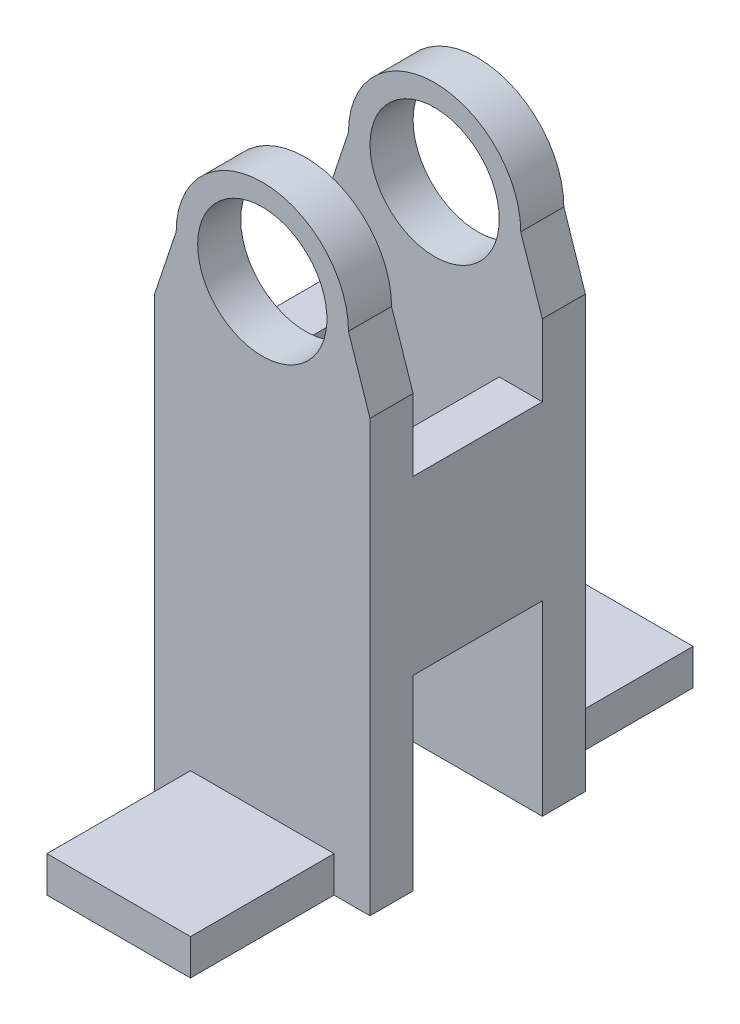
SolidWorks part; units mm, degrees
ref_plane "Front Plane" through (0, 0, 0) normal (0, 0, 1) x (1, 0, 0)
ref_plane "Top Plane" through (0, 0, 0) normal (0, 1, 0) x (1, 0, 0)
ref_plane "Right Plane" through (0, 0, 0) normal (1, 0, 0) x (0, 0, -1)
sketch "Sketch1" plane through (0, 0, 0) normal (0, 1, 0) x (1, 0, 0)
  line L0 (4.5, -4.5) -> (4.5, 4.5)
  line L1 (7.5, -7.5) -> (-7.5, -7.5)
  line L2 (7.5, -7.5) -> (7.5, 7.5)
  line L3 (7.5, 7.5) -> (-7.5, 7.5)
  line L4 (-7.5, -7.5) -> (-7.5, 7.5)
  line L5 (7.5, -7.5) -> (-7.5, 7.5) construction
  line L6 (7.5, 7.5) -> (-7.5, -7.5) construction
  line L7 (4.5, 4.5) -> (-4.5, 4.5)
  line L8 (-4.5, -4.5) -> (-4.5, 4.5)
  line L9 (4.5, -4.5) -> (-4.5, -4.5)
  point P0 (0, 0)
  dimension "D1" = 15
  dimension "D2" = 15
  dimension "D3" = 3
extrude "Boss-Extrude1" add sketch "Sketch1" along normal blind 30
sketch "Sketch3" plane through (0, 0, -7.5) normal (0, 0, -1) x (-1, 0, 0)
  line L0 (-7.5, 30) -> (7.5, 30) construction
  line L1 (-6, 34.5) -> (-7.5, 30)
  line L2 (-7.5, 30) -> (7.5, 30)
  line L3 (7.5, 30) -> (6, 34.5)
  line L4 (7.5, 30) -> (7.5, 0) construction
  line L5 (-7.5, 30) -> (7.5, 30)
  line L6 (-7.5, 30) -> (-7.5, 29)
  line L7 (-7.5, 29) -> (7.5, 29)
  line L8 (7.5, 30) -> (7.5, 29)
  circle A0 centre (0, 34.5) radius 4.5
  arc A1 (-6, 34.5) -> (6, 34.5) centre (0, 34.5) cw
  line M10 (7.5, 0) -> (7.5, 30)
  line M11 (7.5, 30) -> (-7.5, 30)
  line M12 (-7.5, 30) -> (-7.5, 0)
  dimension "D1" = 9
  dimension "D2" = 6
  dimension "D3" = 1
extrude "Boss-Extrude3" add sketch "Sketch3" against normal up to surface (3 mm away) contours A1 L1 L5 A0 L3 M11 | L7 L5 M12 M10 M11 region at (0, 40.3169, -7.5) region at (0, 29.5, -7.5) up to face at (0, 15, -4.5)
extrude "Boss-Extrude4" add sketch "Sketch3<4>" along normal up to surface (-12 mm away) from surface contours A1 L1 L5 A0 L3 M11 | L7 L5 M12 M10 M11 region at (0, 40.3169, -7.5) region at (0, 29.5, -7.5) up to face at (0, 15, 4.5) starting at face at (0, 15, 7.5)
sketch "Sketch3<4>" plane through (0, 0, -7.5) normal (0, 0, -1) x (-1, 0, 0) same geometry as "Sketch3"
sketch "Sketch5" plane through (7.5, 0, 0) normal (1, 0, 0) x (0, 0, -1)
  line L1 (-4.5, 0) -> (4.5, 0)
  line L2 (-4.5, 0) -> (-4.5, 13)
  line L3 (-4.5, 13) -> (4.5, 13)
  line L4 (-4.5, 0) -> (4.5, 0)
  line L5 (-4.5, 30) -> (-4.5, 0)
  line L6 (4.5, 30) -> (-4.5, 30)
  line L7 (4.5, 0) -> (4.5, 30)
  line L8 (-4.5, 0) -> (4.5, 0) construction
  line L9 (-4.5, 30) -> (-4.5, 0) construction
  line L10 (4.5, 30) -> (-4.5, 30) construction
  line L11 (4.5, 0) -> (4.5, 30) construction
  line L12 (4.5, 0) -> (4.5, 13)
  dimension "D2" = 13
  dimension "D1" = 0
extrude "Cut-Extrude2" cut sketch "Sketch5" against normal up to next
sketch "Sketch6" plane through (0, 0, -4.5) normal (0, 0, 1) x (1, 0, 0)
  line L0 (7.5, 13) -> (7.5, 0) construction
  line L1 (7.5, 13) -> (7.5, 0) construction
  line L2 (7.5, 13) -> (-7.5, 13) construction
  line L3 (-7.5, 30) -> (-7.5, 0) construction
  circle A0 centre (0, 11) radius 2
  dimension "D1" = 4
extrude "Boss-Extrude6" add sketch "Sketch6" along normal up to surface (9 mm away) up to face at (1.5, 22.1, 4.5)
sketch "Sketch7" plane through (7.5, 0, 0) normal (1, 0, 0) x (0, 0, -1)
  line L0 (-4.5, 34.5) -> (-4.5, 30) construction
  line L1 (4.5, 30) -> (-4.5, 30)
  line L2 (4.5, 30) -> (4.5, 25)
  line L3 (4.5, 25) -> (-4.5, 25)
  line L4 (-4.5, 30) -> (-4.5, 25)
  dimension "D1" = 5
extrude "Cut-Extrude3" cut sketch "Sketch7" against normal through all
sketch "Sketch8" plane through (0, 0, 0) normal (0, -1, 0) x (1, 0, 0)
  line L0 (-7.5, 7.5) -> (7.5, 7.5) construction
  line L1 (-5, 7.5) -> (5, 7.5)
  line L2 (-5, 7.5) -> (-5, 17.5)
  line L3 (-5, 17.5) -> (5, 17.5)
  line L4 (5, 7.5) -> (5, 17.5)
  line L5 (7.5, -7.5) -> (-7.5, -7.5) construction
  line L6 (-5, -7.5) -> (5, -7.5)
  line L7 (-5, -7.5) -> (-5, -17.5)
  line L8 (-5, -17.5) -> (5, -17.5)
  line L9 (5, -7.5) -> (5, -17.5)
  point P12 (0, 7.5)
  point P14 (0, -7.5)
  dimension "D1" = 10
extrude "Boss-Extrude7" add sketch "Sketch8" against normal blind 2.5
